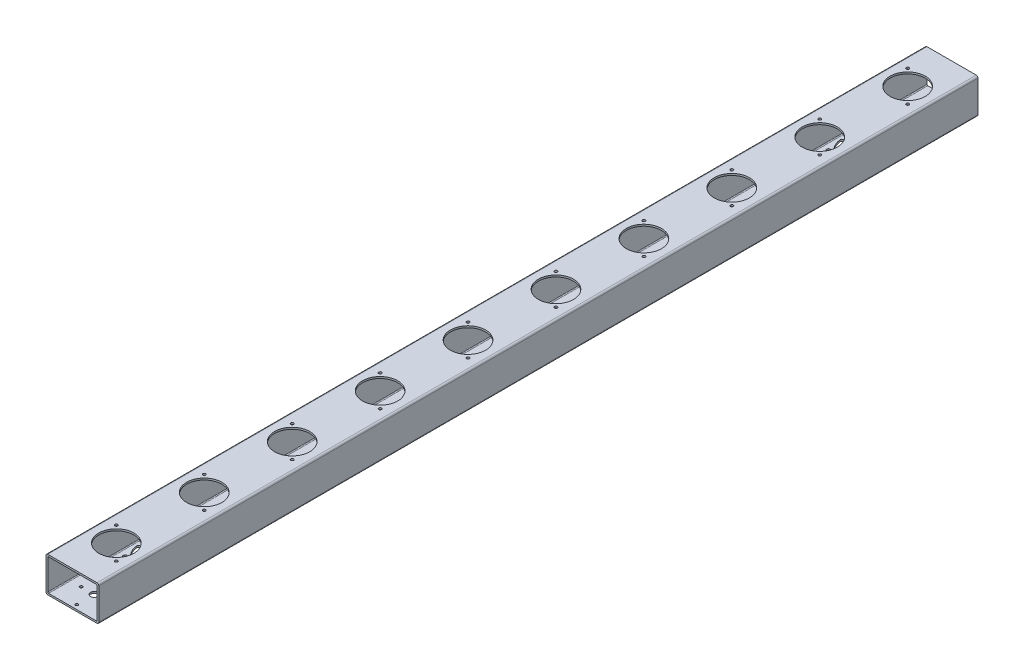
SolidWorks part; units mm, degrees
ref_plane "Plan de face" through (0, 0, 0) normal (0, 0, 1) x (1, 0, 0)
ref_plane "Plan de dessus" through (0, 0, 0) normal (0, 1, 0) x (1, 0, 0)
ref_plane "Plan de droite" through (0, 0, 0) normal (1, 0, 0) x (0, 0, -1)
sketch "Esquisse1" plane through (0, 0, 0) normal (0, 0, 1) x (1, 0, 0)
  line L0 (2, 2) -> (58, 2)
  line L1 (0, 0) -> (60, 0)
  line L2 (0, 0) -> (0, 40)
  line L3 (0, 40) -> (60, 40)
  line L4 (60, 0) -> (60, 40)
  line L5 (58, 2) -> (58, 38)
  line L6 (2, 38) -> (58, 38)
  line L7 (2, 2) -> (2, 38)
  dimension "D1" = 60
  dimension "D2" = 40
  dimension "D3" = 2
extrude "Boss.-Extru.1" add sketch "Esquisse1" along normal blind 1000
fillet "Congé1" radius 1 4 edges at (58, 2, 500) (58, 38, 500) (2, 38, 500) (2, 2, 500)
fillet "Congé2" radius 2 4 edges at (60, 0, 500) (0, 0, 500) (60, 40, 500) (0, 40, 500)
sketch "Esquisse2" plane through (0, 40, 0) normal (0, 1, 0) x (1, 0, 0)
  line L0 (30, 0) -> (30, -50) construction
  line L1 (58, 0) -> (2, 0) construction
  circle A0 centre (30, -50) radius 20
  circle A1 centre (30, -150) radius 20
  circle A2 centre (30, -250) radius 20
  circle A3 centre (30, -350) radius 20
  circle A4 centre (30, -450) radius 20
  circle A5 centre (30, -550) radius 20
  circle A6 centre (30, -650) radius 20
  circle A7 centre (30, -750) radius 20
  circle A8 centre (30, -850) radius 20
  circle A9 centre (30, -950) radius 20
  dimension "D1" = 40
  dimension "D2" = 50
  dimension "D4" = 100
  dimension "D3" = 10
extrude "Enlèv. mat.-Extru.1" cut sketch "Esquisse2" against normal up to next
sketch "Esquisse3" plane through (0, 0, 0) normal (0, -1, 0) x (1, 0, 0)
  line L0 (30, 975) -> (30, 1000) construction
  line L1 (2, 1000) -> (58, 1000) construction
  line L2 (30, 25) -> (30, 0) construction
  line L3 (2, 0) -> (58, 0) construction
  line L4 (30, 975) -> (30, 25) construction
  circle A0 centre (30, 975) radius 4.25
  circle A1 centre (30, 25) radius 4.25
  circle A2 centre (30, 500) radius 4.25
  dimension "D2" = 8.5
  dimension "D1" = 25
extrude "Enlèv. mat.-Extru.2" cut sketch "Esquisse3" against normal up to next
sketch "Esquisse4" plane through (0, 40, 0) normal (0, 1, 0) x (1, 0, 0)
  line L0 (12.3223, -32.3223) -> (47.6777, -67.6777) construction
  line L1 (2, 0) -> (2, -1000) construction
  circle A0 centre (30, -50) radius 25 construction
  circle A1 centre (30, -50) radius 20 construction
  circle A2 centre (12.3223, -32.3223) radius 1.6
  circle A3 centre (47.6777, -67.6777) radius 1.6
  point P6 (30, -50)
  dimension "D1" = 50
  dimension "D3" = 3.2
  dimension "D2" = 45
extrude "Enlèv. mat.-Extru.3" cut sketch "Esquisse4" against normal up to next
sketch "Esquisse6" plane through (0, 0, 0) normal (0, -1, 0) x (-1, 0, 0)
  line L0 (-20, -400) -> (-40, -400) construction
  line L1 (0, -400) -> (-20, -400) construction
  line L3 (0, 0) -> (0, -1000) construction
  line L4 (-40, -400) -> (-60, -400) construction
  line L5 (-60, -1000) -> (-60, 0) construction
  line L6 (-30, -370) -> (-30, -400) construction
  line L7 (-30, -400) -> (-30, -430) construction
  circle A0 centre (-20, -400) radius 1.6
  circle A1 centre (-40, -400) radius 1.6
  circle A2 centre (-30, -350) radius 20 construction
  circle A3 centre (-30, -450) radius 20 construction
  dimension "D2" = 3.2
  dimension "D1" = 20
extrude "Enlèv. mat.-Extru.4" cut sketch "Esquisse6" against normal up to next
pattern_linear "Répétition linéaire1" count 3 spacing 200 along (0, 0, 1) count 2 spacing 200 along (0, 0, -1) of "Enlèv. mat.-Extru.4"
sketch "Esquisse7" plane through (0, 0, 0) normal (0, -1, 0) x (-1, 0, 0)
  line L0 (-15, -500) -> (-45, -500) construction
  line L1 (-15, -975) -> (-45, -975) construction
  line L2 (-15, -25) -> (-45, -25) construction
  circle A0 centre (-15, -25) radius 1.6
  circle A1 centre (-45, -25) radius 1.6
  circle A2 centre (-15, -500) radius 1.6
  circle A3 centre (-45, -500) radius 1.6
  circle A4 centre (-15, -975) radius 1.6
  circle A5 centre (-45, -975) radius 1.6
  point P2 (-30, -500)
  point P3 (-30, -975)
  point P7 (-30, -25)
  dimension "D1" = 3.2
  dimension "D2" = 30
extrude "Enlèv. mat.-Extru.5" cut sketch "Esquisse7" against normal up to next
pattern_linear "Répétition linéaire2" count 10 spacing 100 along (0, 0, 1) of "Enlèv. mat.-Extru.3"
sketch "Esquisse8" plane through (0, 0, 0) normal (0, -1, 0) x (-1, 0, 0)
  circle A0 centre (-22, -44.8174) radius 1.4
  circle A1 centre (-38, -44.8174) radius 1.4
  circle A2 centre (-38, -44.8174) radius 1.25 construction
  circle A3 centre (-22, -44.8174) radius 1.25 construction
  dimension "D1" = 2.8
sketch "Esquisse9" plane through (0, 0, 0) normal (0, -1, 0) x (1, 0, 0)
  line L0 (20.4, 959.6) -> (39.6, 940.4) construction
  line L5 (0, 0) -> (0, 1000) construction
  circle A1 centre (30, 950) radius 13.5765 construction
  circle A2 centre (30, 950) radius 20 construction
  circle A3 centre (20.4, 959.6) radius 1.6
  circle A4 centre (39.6, 940.4) radius 1.6
  dimension "D1" = 3.2
  dimension "D2" = 19.2
  dimension "D3" = 45
extrude "Enlèv. mat.-Extru.6" cut sketch "Esquisse9" against normal up to next
pattern_linear "Répétition linéaire3" count 10 spacing 100 along (0, 0, -1) of "Enlèv. mat.-Extru.6"
sketch "Esquisse10" plane through (0, 0, 0) normal (0, -1, 0) x (1, 0, 0)
  line L0 (20.4, 59.6) -> (20.4, 80) construction
  line L1 (10, 80) -> (50, 80) construction
  line L2 (10, 80) -> (10, 120) construction
  line L3 (10, 120) -> (50, 120) construction
  line L4 (50, 80) -> (50, 120) construction
  line L5 (39.6, 140.4) -> (39.6, 120) construction
  line L6 (0, 100) -> (10, 100) construction
  line L7 (0, 0) -> (0, 1000) construction
  line L8 (50, 100) -> (60, 100) construction
  line L9 (60, 1000) -> (60, 0) construction
  circle A0 centre (10, 120) radius 2.1
  circle A1 centre (50, 120) radius 2.1
  circle A2 centre (50, 80) radius 2.1
  circle A3 centre (10, 80) radius 2.1
  dimension "D2" = 4.2
  dimension "D1" = 40
extrude "Enlèv. mat.-Extru.7" cut sketch "Esquisse10" against normal up to next
pattern_linear "Répétition linéaire4" count 2 spacing 800 along (0, 0, 1) of "Enlèv. mat.-Extru.7"
sketch "Esquisse11" plane through (0, 0, 0) normal (0, -1, 0) x (1, 0, 0)
  line L1 (30, 910) -> (30, 916) construction
  line L2 (30, 918) -> (30, 924) construction
  line L3 (12.0278, 899) -> (6.0208, 899)
  line L4 (20.0501, 899) -> (14.0313, 899)
  line L6 (20.0501, 901) -> (14.0313, 901)
  line L8 (12.0278, 901) -> (6.0208, 901)
  line L9 (20.0501, 901) -> (20.0501, 899) construction
  line L10 (38.1201, 916.0644) -> (41.1236, 921.2666)
  line L11 (39.8521, 915.0644) -> (42.8556, 920.2666)
  line L12 (35.841, 908.1168) -> (38.8504, 913.3293)
  line L13 (34.1089, 909.1168) -> (37.1183, 914.3293)
  line L14 (39.8521, 884.9356) -> (42.8556, 879.7334)
  line L15 (38.1201, 883.9356) -> (41.1236, 878.7334)
  line L16 (34.1089, 890.8832) -> (37.1183, 885.6707)
  line L17 (35.841, 891.8832) -> (38.8504, 886.6707)
  arc A0 (41.1236, 921.2666) -> (42.8556, 920.2666) centre (30, 900) ccw
  arc A1 (20.0501, 899) -> (34.1089, 890.8832) centre (30, 900) ccw
  arc A2 (14.0313, 899) -> (37.1183, 885.6707) centre (30, 900) ccw
  arc A3 (12.0278, 899) -> (38.1201, 883.9356) centre (30, 900) ccw
  arc A4 (24.1103, 908.0815) -> (20.0094, 900.434) centre (30, 900) ccw construction
  arc A5 (39.8521, 884.9356) -> (39.8521, 915.0644) centre (30, 900) ccw
  arc A6 (38.8504, 886.6707) -> (38.8504, 913.3293) centre (30, 900) ccw
  arc A7 (35.841, 891.8832) -> (35.841, 908.1168) centre (30, 900) ccw
  arc A8 (38.1201, 916.0644) -> (12.0278, 901) centre (30, 900) ccw
  arc A9 (37.1183, 914.3293) -> (14.0313, 901) centre (30, 900) ccw
  arc A10 (34.1089, 909.1168) -> (20.0501, 901) centre (30, 900) ccw
  dimension "D1" = 48
  dimension "D2" = 20
  dimension "D3" = 2
  dimension "D4" = 2
  dimension "D5" = 3
extrude "Enlèv. mat.-Extru.8" cut sketch "Esquisse11" against normal up to next contours A8 L10 A0 L8 | A3 L3 A0 L15 | A5 L14 A0 L11 | L4 A2 L16 A1 | A7 L17 A6 L12 | A10 L13 A9 L6 region at (20.7902, 0, 884.0481) region at (41.7257, 0, 882.5492) region at (18.2098, 0, 920.4212) region at (24.3698, 0, 890.2482) region at (24.3698, 0, 909.7518) region at (41.2604, 0, 900)
fillet "Congé3" radius 2 24 edges at (6.0208, 1, 899) (12.0278, 1, 899) (14.0313, 1, 899) (20.0501, 1, 899) (34.1089, 1, 890.8832) (37.1183, 1, 885.6707) (38.1201, 1, 883.9356) (41.1236, 1, 878.7334) (42.8556, 1, 879.7334) (38.8504, 1, 886.6707) (39.8521, 1, 884.9356) (35.841, 1, 891.8832) (39.8521, 1, 915.0644) (42.8556, 1, 920.2666) (35.841, 1, 908.1168) (38.8504, 1, 913.3293) (34.1089, 1, 909.1168) (37.1183, 1, 914.3293) (20.0501, 1, 901) (14.0313, 1, 901) (6.0208, 1, 901) (12.0278, 1, 901) (38.1201, 1, 916.0644) (41.1236, 1, 921.2666)
pattern_linear "Répétition linéaire5" count 2 spacing 800 along (0, 0, -1) of "Enlèv. mat.-Extru.8", "Congé3"
sketch "Esquisse12" plane through (0, 0, 0) normal (0, -1, 0) x (1, 0, 0)
  line L0 (39.6, 740.4) -> (39.6, 735) construction
  line L1 (10, 735) -> (50, 735) construction
  line L2 (10, 735) -> (10, 665) construction
  line L3 (10, 665) -> (50, 665) construction
  line L4 (50, 735) -> (50, 665) construction
  line L5 (20.4, 659.6) -> (20.4, 665) construction
  line L6 (10, 700) -> (0, 700) construction
  line L7 (50, 700) -> (60, 700) construction
  line L8 (60, 1000) -> (60, 0) construction
  line L9 (0, 0) -> (0, 1000) construction
  circle A0 centre (10, 735) radius 1.6
  circle A1 centre (50, 735) radius 1.6
  circle A2 centre (50, 665) radius 1.6
  circle A3 centre (10, 665) radius 1.6
  dimension "D1" = 3.2
  dimension "D2" = 40
  dimension "D3" = 70
extrude "Enlèv. mat.-Extru.9" cut sketch "Esquisse12" against normal up to next
sketch "Esquisse13" plane through (0, 0, 0) normal (0, -1, 0) x (1, 0, 0)
  line L0 (17, 717) -> (0, 717) construction
  line L1 (17, 724) -> (43, 724)
  line L2 (17, 724) -> (17, 710)
  line L3 (17, 710) -> (43, 710)
  line L4 (43, 724) -> (43, 710)
  line L5 (0, 0) -> (0, 1000) construction
  line L6 (43, 717) -> (60, 717) construction
  line L7 (60, 1000) -> (60, 0) construction
  line L9 (30, 700) -> (30, 710) construction
  line L10 (17, 700) -> (30, 700) construction
  line L11 (30, 700) -> (43, 700) construction
  circle A0 centre (17, 700) radius 1.9
  circle A1 centre (30, 700) radius 1.9
  circle A2 centre (43, 700) radius 1.9
  circle A3 centre (10, 735) radius 1.6 construction
  dimension "D6" = 3.8
  dimension "D3" = 18
  dimension "D1" = 26
  dimension "D2" = 14
  dimension "D4" = 13
  dimension "D5" = 10
extrude "Enlèv. mat.-Extru.10" cut sketch "Esquisse13" against normal up to next
sketch "Esquisse14" plane through (0, 0, 0) normal (0, -1, 0) x (1, 0, 0)
  line L0 (30, 995) -> (30, 1000) construction
  line L1 (2, 1000) -> (58, 1000) construction
  line L2 (30, 5) -> (30, 0) construction
  line L3 (2, 0) -> (58, 0) construction
  circle A0 centre (30, 5) radius 1.6
  circle A1 centre (30, 995) radius 1.6
  dimension "D1" = 3.2
  dimension "D2" = 5
extrude "Enlèv. mat.-Extru.11" cut sketch "Esquisse14" against normal up to next
sketch "Esquisse15" plane through (0, 0, 0) normal (0, -1, 0) x (1, 0, 0)
  line L4 (20, 400) -> (40, 400) construction
  line L5 (30, 425) -> (30, 400) construction
  circle A3 centre (30, 425) radius 2.5
  dimension "D3" = 5
  dimension "D4" = 25
extrude "Enlèv. mat.-Extru.12" cut sketch "Esquisse15" against normal up to next
